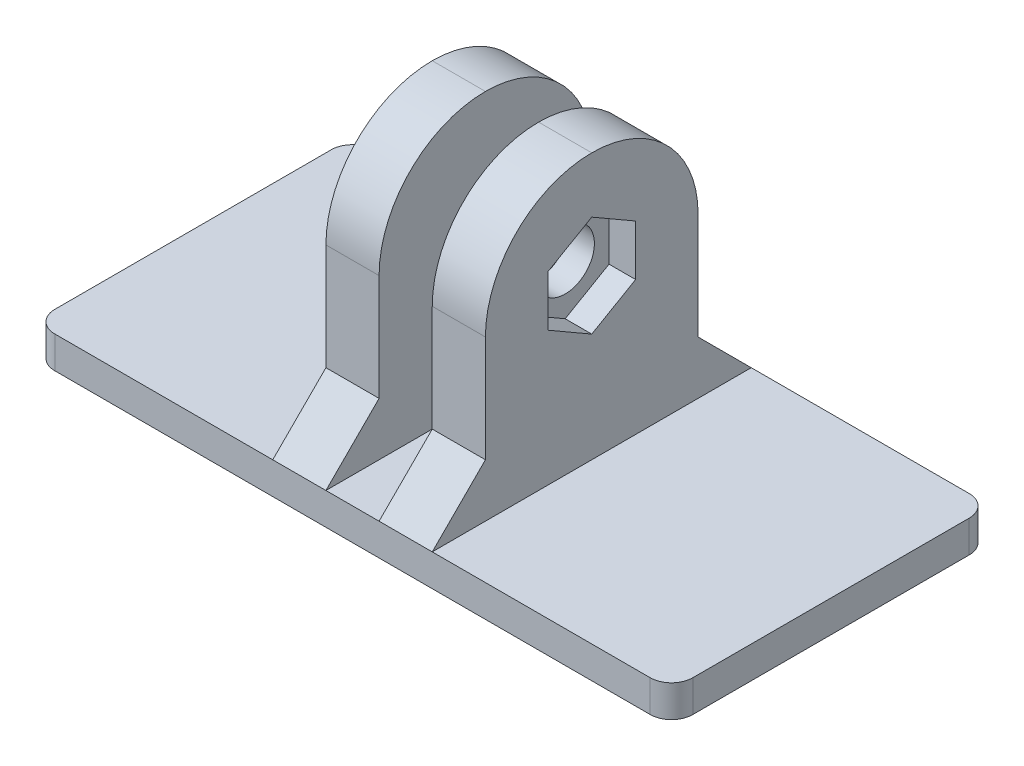
SolidWorks part; units mm, degrees
ref_plane "Front Plane" through (0, 0, 0) normal (0, 0, 1) x (1, 0, 0)
ref_plane "Top Plane" through (0, 0, 0) normal (0, 1, 0) x (1, 0, 0)
ref_plane "Right Plane" through (0, 0, 0) normal (1, 0, 0) x (0, 0, -1)
sketch "Sketch1" plane through (0, 0, 0) normal (0, 1, 0) x (1, 0, 0)
  line L0 (0, 15) -> (0, -15) construction
  line L1 (-30, 15) -> (30, 15)
  line L2 (-30, 15) -> (-30, -15)
  line L3 (-30, -15) -> (30, -15)
  line L4 (30, 15) -> (30, -15)
  dimension "D1" = 30
  dimension "D2" = 60
extrude "Boss-Extrude1" add sketch "Sketch1" along normal blind 3
fillet "Fillet2" radius 2 4 edges at (30, 1.5, -15) (30, 1.5, 15) (-30, 1.5, 15) (-30, 1.5, -15)
sketch "Sketch4" plane through (0, 3, 0) normal (0, 1, 0) x (1, 0, 0)
  line L0 (0, 15) -> (0, -15) construction
  line L1 (28, 15) -> (-28, 15) construction
  line L2 (-28, -15) -> (28, -15) construction
  line L3 (-30, 0) -> (0, 0) construction
  line L4 (-2.5, 10) -> (-7.5, 10)
  line L5 (-2.5, 10) -> (-2.5, -10)
  line L6 (-2.5, -10) -> (-7.5, -10)
  line L7 (-7.5, 10) -> (-7.5, -10)
  line L8 (-30, 13) -> (-30, -13) construction
  line L9 (7.5, 10) -> (7.5, -10)
  line L10 (2.5, -10) -> (7.5, -10)
  line L11 (2.5, 10) -> (2.5, -10)
  line L12 (2.5, 10) -> (7.5, 10)
  point P15 (-2.5, 0)
  dimension "D1" = 5
  dimension "D2" = 2.5
  dimension "D3" = 20
extrude "Boss-Extrude2" add sketch "Sketch4" along normal blind 25
fillet "Fillet3" radius 10 4 edges at (5, 28, 10) (5, 28, -10) (-5, 28, -10) (-5, 28, 10)
sketch "Sketch5" plane through (-7.5, 0, 0) normal (-1, 0, 0) x (0, 0, 1)
  circle A0 centre (0, 18) radius 2.75
  arc A1 (10, 18) -> (0, 28) centre (0, 18) ccw construction
  dimension "D1" = 5.5
extrude "Cut-Extrude3" cut sketch "Sketch5" against normal through all both and the other way through all
sketch "Sketch6" plane through (7.5, 0, 0) normal (1, 0, 0) x (0, 0, -1)
  line L1 (0, 13.2369) -> (4.125, 15.6184)
  line L2 (4.125, 15.6184) -> (4.125, 20.3816)
  line L3 (4.125, 20.3816) -> (0, 22.7631)
  line L4 (0, 22.7631) -> (-4.125, 20.3816)
  line L5 (-4.125, 20.3816) -> (-4.125, 15.6184)
  line L6 (-4.125, 15.6184) -> (0, 13.2369)
  circle A0 centre (0, 18) radius 4.125 construction
  dimension "D1" = 8.25
extrude "Cut-Extrude4" cut sketch "Sketch6" against normal blind 2.5
chamfer "Chamfer1" distance 5 angle 45 4 edges at (5, 3, -10) (-5, 3, -10) (-5, 3, 10) (5, 3, 10)
